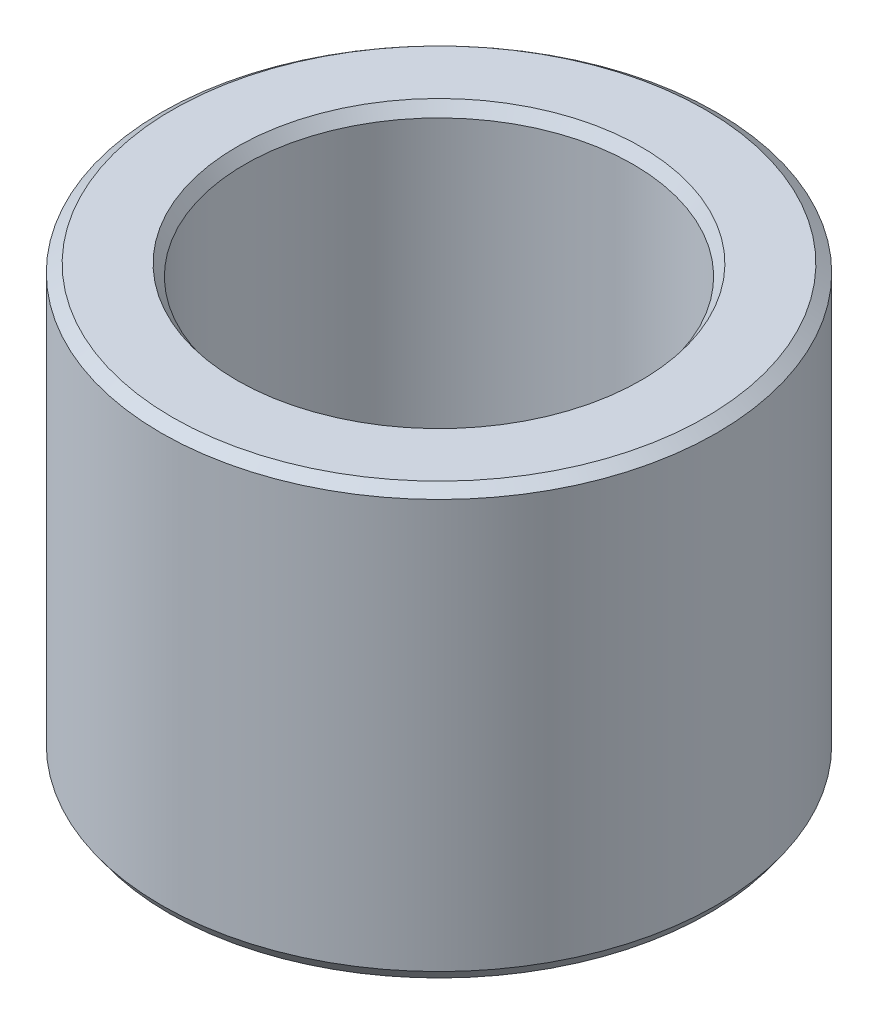
SolidWorks part; units mm, degrees
ref_plane "Front Plane" through (0, 0, 0) normal (0, 0, 1) x (1, 0, 0)
ref_plane "Top Plane" through (0, 0, 0) normal (0, 1, 0) x (1, 0, 0)
ref_plane "Right Plane" through (0, 0, 0) normal (1, 0, 0) x (0, 0, -1)
sketch "Sketch1" plane through (0, 0, 0) normal (0, 1, 0) x (1, 0, 0)
  circle A0 centre (0, 0) radius 45
  dimension "SLEEVE_OD" = 90
extrude "Boss-Extrude1" add sketch "Sketch1" along normal blind 69.3564
sketch "Sketch2" plane through (0, 0, 0) normal (0, 1, 0) x (1, 0, 0)
  circle A0 centre (0, 0) radius 31.4702
  dimension "BORE_D" = 62.9403
extrude "Cut-Extrude1" cut sketch "Sketch2" along normal through all
chamfer "Chamfer1" distance 1.2919 angle 54.559 4 edges at (0, 69.3564, 31.4702) (0, 0, 31.4702) (0, 0, 45) (0, 69.3564, 45) first distance on face at (0, 69.3564, 31.4702) first distance on face at (0, 0, 31.4702) first distance on face at (0, 69.3564, 45)
